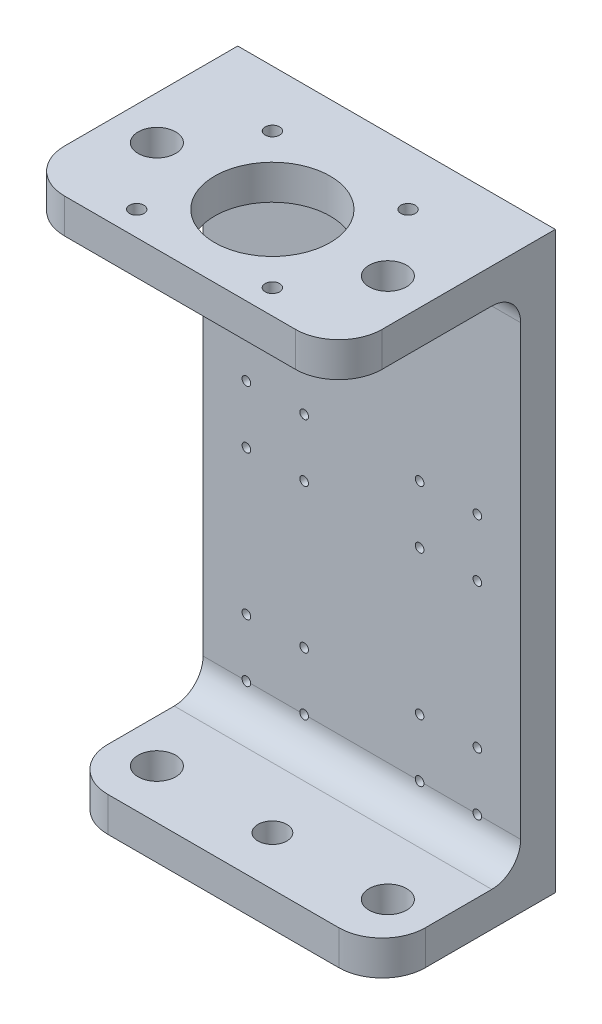
SolidWorks part; units mm, degrees
ref_plane "Front Plane" through (0, 0, 0) normal (0, 0, 1) x (1, 0, 0)
ref_plane "Top Plane" through (0, 0, 0) normal (0, 1, 0) x (1, 0, 0)
ref_plane "Right Plane" through (0, 0, 0) normal (1, 0, 0) x (0, 0, -1)
sketch "Sketch1" plane through (0, 0, 0) normal (0, 0, 1) x (1, 0, 0)
  line L0 (55, 0) -> (55, 87.4837) construction
  line L1 (0, 0) -> (110, 0)
  line L2 (0, 0) -> (0, 175)
  line L3 (0, 175) -> (110, 175)
  line L4 (110, 0) -> (110, 175)
  line L5 (75, 20) -> (104.7449, 20) construction
  line L6 (-2.4027, 55) -> (104.7449, 55) construction
  circle A0 centre (95, 10) radius 1.5
  circle A1 centre (75, 10) radius 1.5
  circle A2 centre (95, 30) radius 1.5
  circle A3 centre (75, 30) radius 1.5
  circle A4 centre (35, 10) radius 1.5
  circle A5 centre (15, 10) radius 1.5
  circle A6 centre (15, 30) radius 1.5
  circle A7 centre (35, 30) radius 1.5
  circle A8 centre (95, 100) radius 1.5
  circle A9 centre (95, 80) radius 1.5
  circle A10 centre (75, 80) radius 1.5
  circle A11 centre (75, 100) radius 1.5
  circle A12 centre (35, 100) radius 1.5
  circle A13 centre (15, 100) radius 1.5
  circle A14 centre (35, 80) radius 1.5
  circle A15 centre (15, 80) radius 1.5
  dimension "D3" = 3
  dimension "D1" = 110
  dimension "D2" = 175
  dimension "D4" = 20
  dimension "D5" = 15
  dimension "D6" = 10
  dimension "D7" = 10
  dimension "D8" = 35
extrude "Boss-Extrude1" add sketch "Sketch1" along normal blind 12
sketch "Sketch2" plane through (0, 0, 0) normal (0, 0, -1) x (-1, 0, 0)
  line L1 (-110, 175) -> (0, 175)
  line L2 (-110, 175) -> (-110, 187)
  line L3 (-110, 187) -> (0, 187)
  line L4 (0, 175) -> (0, 187)
  line L5 (-110, 0) -> (0, 0)
  line L6 (-110, 0) -> (-110, -12)
  line L7 (-110, -12) -> (0, -12)
  line L8 (0, 0) -> (0, -12)
  line M18 (0, 175) -> (-110, 175)
  line M20 (-110, 0) -> (0, 0)
  dimension "D1" = 12
  dimension "D2" = 12
extrude "Boss-Extrude2" add sketch "Sketch2" against normal blind 75 contours L4 L3 L2 M18 region at (55, 181, 0)
extrude "Boss-Extrude3" add sketch "Sketch2<3>" against normal blind 60 contours L8 L6 L7 M20 region at (55, -6, 0)
sketch "Sketch2<3>" plane through (0, 0, 0) normal (0, 0, -1) x (-1, 0, 0) same geometry as "Sketch2"
sketch "Sketch3" plane through (0, 187, 0) normal (0, 1, 0) x (1, 0, 0)
  line L0 (0, -43) -> (110, -43) construction
  line L1 (0, -75) -> (0, 0) construction
  line L2 (110, -75) -> (110, 0) construction
  line L4 (0, -12) -> (110, -12) construction
  line L6 (110, -75) -> (0, -75) construction
  line L7 (78.5, -66.5) -> (31.5, -66.5) construction
  line L8 (78.5, -66.5) -> (78.5, -19.5) construction
  line L9 (78.5, -19.5) -> (31.5, -19.5) construction
  line L10 (31.5, -66.5) -> (31.5, -19.5) construction
  line L11 (78.5, -66.5) -> (31.5, -19.5) construction
  line L12 (78.5, -19.5) -> (31.5, -66.5) construction
  line L13 (110, 0) -> (0, 0) construction
  circle A0 centre (55, -43) radius 20
  circle A1 centre (15, -43) radius 6.5
  circle A2 centre (95, -43) radius 6.5
  circle A5 centre (31.5, -19.5) radius 2.5
  circle A6 centre (78.5, -19.5) radius 2.5
  circle A7 centre (31.5, -66.5) radius 2.5
  circle A8 centre (78.5, -66.5) radius 2.5
  circle A9 centre (55, -43) radius 5
  dimension "D3" = 13
  dimension "D4" = 10
  dimension "D6" = 40
  dimension "D11" = 5
  dimension "D9" = 80
  dimension "D2" = 12
  dimension "D5" = 15
  dimension "D7" = 15
  dimension "D8" = 47
  dimension "D12" = 32
extrude "Cut-Extrude1" cut sketch "Sketch3" against normal through all contours A1 | A2 region at (15, 187, 43) region at (95, 187, 43)
extrude "Cut-Extrude2" cut sketch "Sketch3<3>" against normal up to next contours A5 | A6 | A7 | A8 | A0 region at (31.5, 187, 19.5) region at (78.5, 187, 19.5) region at (31.5, 187, 66.5) region at (78.5, 187, 66.5)
sketch "Sketch3<3>" plane through (0, 187, 0) normal (0, 1, 0) x (1, 0, 0) same geometry as "Sketch3"
extrude "Cut-Extrude3" cut sketch "Sketch3<4>" against normal through all contours A9 region at (55, 187, 43)
sketch "Sketch3<4>" plane through (0, 187, 0) normal (0, 1, 0) x (1, 0, 0) same geometry as "Sketch3"
fillet "Fillet1" radius 10 2 edges at (55, 175, 12) (55, 0, 12)
fillet "Fillet2" radius 15 4 edges at (110, 181, 75) (0, 181, 75) (110, -6, 60) (0, -6, 60)
